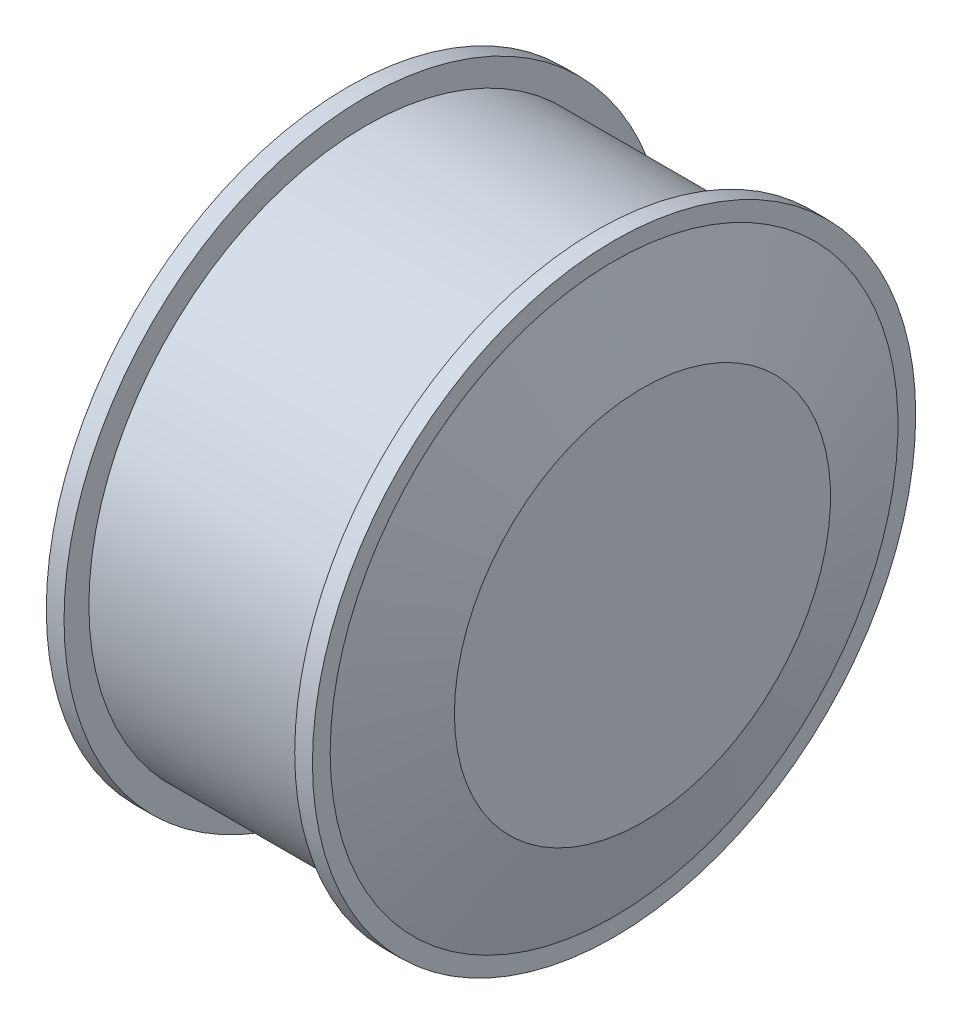
SolidWorks part; units mm, degrees
ref_plane "Спереди" through (0, 0, 0) normal (0, 0, 1) x (1, 0, 0)
ref_plane "Сверху" through (0, 0, 0) normal (0, 1, 0) x (1, 0, 0)
ref_plane "Справа" through (0, 0, 0) normal (1, 0, 0) x (0, 0, -1)
sketch "Эскиз1" plane through (0, 0, 0) normal (0, 0, 1) x (1, 0, 0)
  line L0 (-1100.9037, 0) -> (53944.2801, 0) construction
  line L1 (0, -1100.9037) -> (0, 53944.2801) construction
  line L2 (-32.5, 100) -> (32.5, 100) construction
  line L3 (32.5, 100) -> (32.5, 85) construction
  line L4 (32.5, 85) -> (37.5, 85)
  line L5 (37.5, 85) -> (37.5, 80)
  line L6 (37.5, 80) -> (45.5, 53)
  line L7 (45.5, 53) -> (45.5, 11)
  line L8 (45.5, 11) -> (48.5, 11)
  line L9 (48.5, 11) -> (48.5, 8)
  line L10 (48.5, 8) -> (87.5, 8)
  line L11 (87.5, 8) -> (87.5, 0)
  line L12 (-87.5, 8) -> (-87.5, 0)
  line L13 (-48.5, 8) -> (-87.5, 8)
  line L14 (-48.5, 11) -> (-48.5, 8)
  line L15 (-45.5, 11) -> (-48.5, 11)
  line L16 (-45.5, 53) -> (-45.5, 11)
  line L17 (-37.5, 80) -> (-45.5, 53)
  line L18 (-37.5, 85) -> (-37.5, 80)
  line L19 (-32.5, 85) -> (-37.5, 85)
  line L20 (-32.5, 100) -> (-32.5, 85) construction
  line L21 (87.5, 0) -> (-87.5, 0)
  line L22 (-32.5, 85) -> (-32.5, 78)
  line L23 (-32.5, 78) -> (32.5, 78)
  line L24 (32.5, 78) -> (32.5, 85)
  point P19 (0, 100)
  dimension "D1" = 100
  dimension "D2" = 170
  dimension "D3" = 106
  dimension "D4" = 91
  dimension "D5" = 5
  dimension "D6" = 175
  dimension "D7" = 39
  dimension "D8" = 32.5
  dimension "D9" = 5
  dimension "D10" = 16
  dimension "D11" = 7
revolve "Повернуть1" add sketch "Эскиз1" angle 360 about L0
cosmetic thread "Условное изображение резьбы1" parameters "D2"=14.344
cosmetic thread "Условное изображение резьбы2" parameters "D2"=14.344
sketch "Эскиз2" plane through (0, 0, 0) normal (1, 0, 0) x (0, 0, -1)
  line L0 (-6, 5.2915) -> (-6, -5.2915)
  line L1 (6, 5.2915) -> (6, -5.2915)
  circle A0 centre (0, 0) radius 8 construction
  arc A1 (6, 5.2915) -> (-6, 5.2915) centre (0, 0) ccw
  arc A2 (-6, -5.2915) -> (6, -5.2915) centre (0, 0) ccw
  dimension "D1" = 12
ref_plane "Плоскость1" through (53.5, 0, 0) normal (1, 0, 0) x (0, 0, -1)
ref_plane "Плоскость2" through (-53.5, 0, 0) normal (-1, 0, 0) x (0, 0, 1)
extrude "Вырез-Вытянуть1" cut sketch "Эскиз2" against normal through all from surface flip side to cut starting at plane "Плоскость2"
extrude "Вырез-Вытянуть2" cut sketch "Эскиз2<2>" along normal through all from surface flip side to cut starting at plane "Плоскость1"
sketch "Эскиз2<2>" plane through (0, 0, 0) normal (1, 0, 0) x (0, 0, -1) same geometry as "Эскиз2"
sketch "Эскиз3" plane through (87.5, 0, 0) normal (1, 0, 0) x (0, 0, -1)
  circle A0 centre (0, 0) radius 53 construction
  circle A1 centre (0, 0) radius 53
extrude "Вырез-Вытянуть3" cut sketch "Эскиз3" against normal up to surface (42 mm away) up to face at (45.5, 0, 53)
